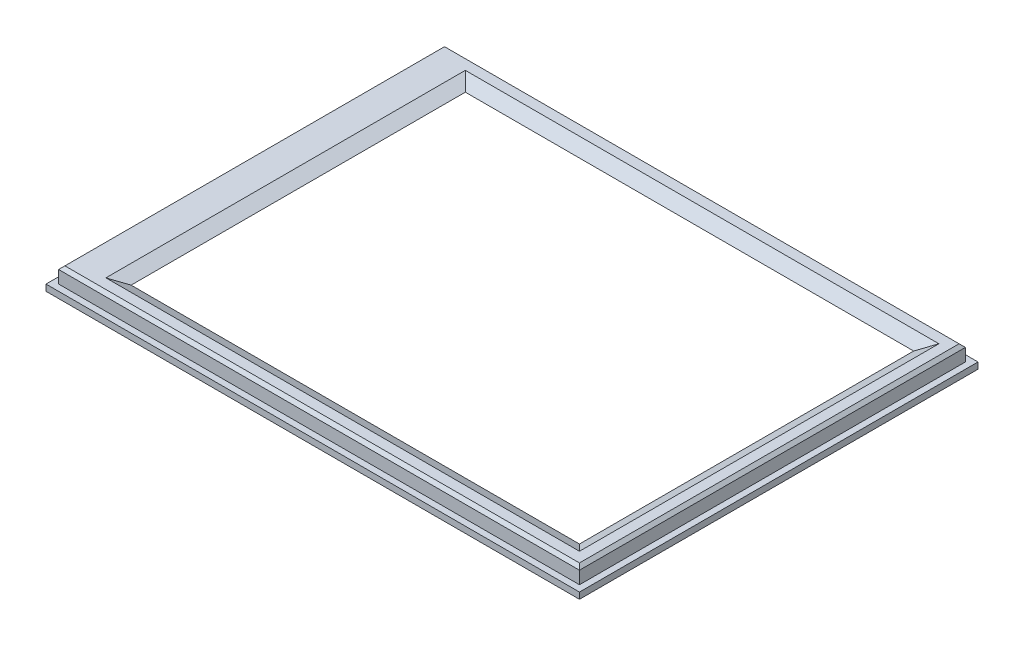
SolidWorks part; units mm, degrees
ref_plane "Front Plane" through (0, 0, 0) normal (0, 0, 1) x (1, 0, 0)
ref_plane "Top Plane" through (0, 0, 0) normal (0, 1, 0) x (1, 0, 0)
ref_plane "Right Plane" through (0, 0, 0) normal (1, 0, 0) x (0, 0, -1)
sketch "Sketch1" plane through (0, 0, 0) normal (0, 1, 0) x (1, 0, 0)
  line L0 (2, 2) -> (82.6, 2)
  line L1 (0, 0) -> (84.6, 0)
  line L2 (0, 0) -> (0, 63.2)
  line L3 (0, 63.2) -> (84.6, 63.2)
  line L4 (84.6, 0) -> (84.6, 63.2)
  line L5 (82.6, 2) -> (82.6, 61.2)
  line L6 (2, 61.2) -> (82.6, 61.2)
  line L7 (2, 2) -> (2, 61.2)
  dimension "D1" = 84.6
  dimension "D2" = 63.2
  dimension "D3" = 2
extrude "Boss-Extrude1" add sketch "Sketch1" along normal blind 1
sketch "Sketch2" plane through (0, 1, 0) normal (0, 1, 0) x (1, 0, 0)
  line L0 (1, 62.2) -> (83.6, 62.2)
  line L1 (2, 61.2) -> (82.6, 61.2)
  line L2 (2, 61.2) -> (2, 2)
  line L3 (2, 2) -> (82.6, 2)
  line L4 (82.6, 61.2) -> (82.6, 2)
  line L5 (83.6, 62.2) -> (83.6, 1)
  line L6 (1, 1) -> (83.6, 1)
  line L7 (1, 62.2) -> (1, 1)
  dimension "D1" = 1
extrude "Boss-Extrude2" add sketch "Sketch2" along normal blind 2.5
sketch "Sketch3" plane through (0, 3.5, 0) normal (0, 1, 0) x (1, 0, 0)
  line L0 (2, 61.2) -> (2, 2) construction
  line L1 (1, 62.2) -> (83.6, 62.2)
  line L2 (1, 62.2) -> (1, 1)
  line L3 (1, 1) -> (83.6, 1)
  line L4 (83.6, 62.2) -> (83.6, 1)
  line L5 (8.4, 58.1) -> (79.5, 58.1)
  line L6 (8.4, 58.1) -> (8.4, 5.1)
  line L7 (8.4, 5.1) -> (79.5, 5.1)
  line L8 (79.5, 58.1) -> (79.5, 5.1)
  line L9 (82.6, 61.2) -> (2, 61.2) construction
  dimension "D1" = 6.4
  dimension "D2" = 3.1
  dimension "D3" = 71.1
  dimension "D4" = 53
extrude "Boss-Extrude3" add sketch "Sketch3" against normal blind 1
chamfer "Chamfer1" distance 2 distance2 1 4 edges at (79.5, 3.5, -31.6) (43.95, 3.5, -5.1) (8.4, 3.5, -31.6) (43.95, 3.5, -58.1) first distance on face at (42.3, 3.5, -31.6)
chamfer "Chamfer2" distance 0.5 angle 45 4 edges at (42.3, 3.5, -1) (83.6, 3.5, -31.6) (42.3, 3.5, -62.2) (1, 3.5, -31.6)
